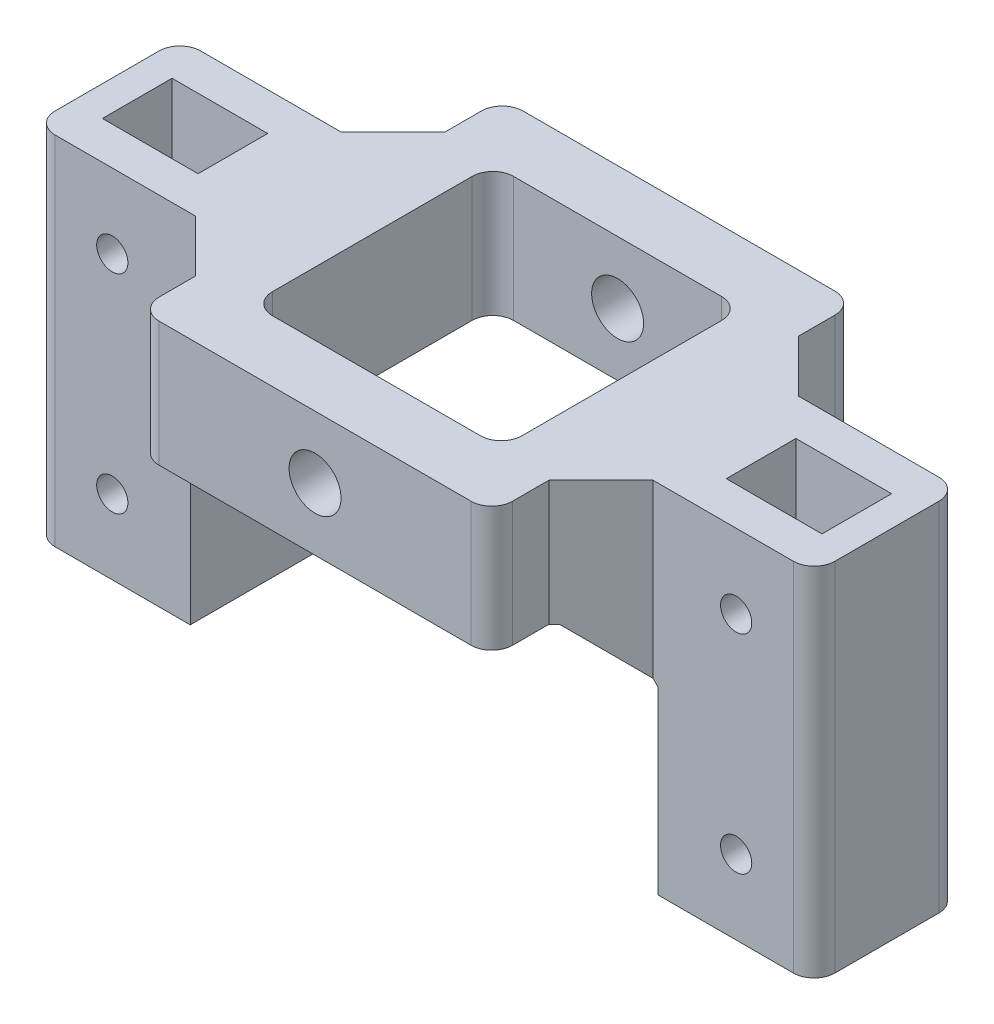
SolidWorks part; units mm, degrees
material "聚脂树脂"
ref_plane "前视基准面" through (0, 0, 0) normal (0, 0, 1) x (1, 0, 0)
ref_plane "上视基准面" through (0, 0, 0) normal (0, 1, 0) x (1, 0, 0)
ref_plane "右视基准面" through (0, 0, 0) normal (1, 0, 0) x (0, 0, -1)
other "Configuration Table"
sketch "草图1" plane through (0, 0, 0) normal (0, 0, 1) x (1, 0, 0)
  line L0 (0, 0) -> (63.4535, 0) construction
  line L5 (-22.5, 17.15) -> (-37.5, -17.15) construction
  line L6 (22.5, -17.15) -> (37.5, -17.15)
  line L7 (0, 0) -> (0, 35.1803) construction
  line L8 (22.5, -17.15) -> (22.5, 17.15)
  line L9 (22.5, 17.15) -> (37.5, 17.15)
  line L10 (37.5, -17.15) -> (37.5, 17.15)
  line L11 (22.5, -17.15) -> (37.5, 17.15) construction
  line L12 (22.5, 17.15) -> (37.5, -17.15) construction
  line L13 (-22.5, -17.15) -> (-37.5, 17.15) construction
  line L14 (-37.5, -17.15) -> (-37.5, 17.15)
  line L15 (-22.5, 17.15) -> (-37.5, 17.15)
  line L16 (-22.5, -17.15) -> (-22.5, 17.15)
  line L17 (-22.5, -17.15) -> (-37.5, -17.15)
  circle A1 centre (30, 10) radius 1.5
  circle A2 centre (30, -10) radius 1.5
  circle A3 centre (-30, -10) radius 1.5
  circle A4 centre (-30, 10) radius 1.5
  point P0 (30, 0)
  point P21 (-30, 0)
  dimension "D3" = 30
  dimension "D4" = 3
  dimension "D1" = 15
  dimension "D2" = 34.3
  dimension "D5" = 30
  dimension "D6" = 10
extrude "凸台-拉伸1" add sketch "草图1" along normal blind 7 and the other way blind 7
sketch "草图2" plane through (0, 17.15, 0) normal (0, 1, 0) x (1, 0, 0)
  line L0 (0, 0) -> (0, 28.9204) construction
  line L1 (0, 0) -> (49.6088, 0) construction
  line L2 (-25.4, 3.35) -> (-34.6, -3.35) construction
  line L3 (25.4, -3.35) -> (34.6, -3.35)
  line L4 (25.4, -3.35) -> (25.4, 3.35)
  line L5 (25.4, 3.35) -> (34.6, 3.35)
  line L6 (34.6, -3.35) -> (34.6, 3.35)
  line L7 (25.4, -3.35) -> (34.6, 3.35) construction
  line L8 (25.4, 3.35) -> (34.6, -3.35) construction
  line L9 (-25.4, -3.35) -> (-34.6, 3.35) construction
  line L10 (-34.6, -3.35) -> (-34.6, 3.35)
  line L11 (-25.4, 3.35) -> (-34.6, 3.35)
  line L12 (-25.4, -3.35) -> (-25.4, 3.35)
  line L13 (-25.4, -3.35) -> (-34.6, -3.35)
  point P3 (30, 0)
  point P13 (-30, 0)
  dimension "D1" = 9.2
  dimension "D2" = 6.7
  dimension "D3" = 30
extrude "切除-拉伸1" cut sketch "草图2" against normal blind 62
sketch "草图3" plane through (0, 17.15, 0) normal (0, 1, 0) x (1, 0, 0)
  line L0 (0, 0) -> (46.7542, 0) construction
  line L1 (0, 0) -> (0, 26.73) construction
  line L2 (22.5, 7) -> (17, 7)
  line L3 (17, 7) -> (17, 17.5)
  line L4 (17, 17.5) -> (-17, 17.5)
  line L6 (-12, 11.6) -> (12, 11.6)
  line L7 (12, 11.6) -> (12, -11.6)
  line L8 (22.5, 7) -> (22.5, -7)
  line L9 (22.5, 7) -> (22.5, -7) construction
  line L10 (-12, -11.6) -> (12, -11.6)
  line L12 (17, -17.5) -> (-17, -17.5)
  line L13 (17, -7) -> (17, -17.5)
  line L14 (22.5, -7) -> (17, -7)
  line L15 (-22.5, -7) -> (-17, -7)
  line L16 (-17, -7) -> (-17, -17.5)
  line L17 (-22.5, 7) -> (-22.5, -7)
  line L18 (-12, 11.6) -> (-12, -11.6)
  line L19 (-17, 7) -> (-17, 17.5)
  line L20 (-22.5, 7) -> (-17, 7)
  point P16 (22.5, 0)
  point P17 (12, 0)
  point P24 (0, -17.5)
  point P25 (0, -11.6)
  point P27 (0, 11.6)
  point P28 (0, 17.5)
  point P29 (-12, 0)
  point P30 (-22.5, 0)
  dimension "D1" = 23.2
  dimension "D2" = 24
  dimension "D3" = 34
  dimension "D4" = 35
extrude "凸台-拉伸2" add sketch "草图3" against normal blind 12
sketch "草图4" plane through (0, 0, 17.5) normal (0, 0, 1) x (1, 0, 0)
  line L0 (0, 0) -> (0, 29.922) construction
  line L1 (-17, 5.15) -> (17, 5.15) construction
  circle A0 centre (0, 11.15) radius 2.5
  dimension "D1" = 5
  dimension "D2" = 6
extrude "切除-拉伸2" cut sketch "草图4" against normal blind 90
sketch "草图6" plane through (0, 0, 7) normal (0, 0, 1) x (1, 0, 0)
  line L0 (0, 0) -> (0, 28.8184) construction
  line L1 (0, 0) -> (51.072, 0) construction
  line L2 (-37.5, 17.15) -> (-37.5, 29.15)
  line L3 (-37.5, 29.15) -> (-22.5, 29.15)
  line L4 (-22.5, 29.15) -> (-22.5, 17.15)
  line L5 (-37.5, 17.15) -> (-17, 17.15) construction
  line L7 (-35, 17.15) -> (-35, 26.65)
  line L8 (-35, 26.65) -> (-25, 26.65)
  line L9 (-25, 26.65) -> (-25, 17.15)
  line L10 (-37.5, 17.15) -> (-35, 17.15)
  line L11 (-25, 17.15) -> (-22.5, 17.15)
  line L12 (25, 26.65) -> (25, 17.15)
  line L13 (35, 26.65) -> (25, 26.65)
  line L14 (35, 17.15) -> (35, 26.65)
  line L15 (37.5, 17.15) -> (35, 17.15)
  line L16 (37.5, 17.15) -> (37.5, 29.15)
  line L17 (37.5, 29.15) -> (22.5, 29.15)
  line L18 (22.5, 29.15) -> (22.5, 17.15)
  line L19 (25, 17.15) -> (22.5, 17.15)
  dimension "D1" = 12
  dimension "D2" = 2.5
fillet "圆角1" radius 2 4 edges at (37.5, 0, -7) (37.5, 0, 7) (-37.5, 0, -7) (-37.5, 0, 7)
chamfer "倒角1" distance 5 angle 45 2 edges at (22.5, 5.15, 0) (-22.5, 5.15, 0)
chamfer "倒角2" distance 5 angle 45 4 edges at (17, 11.15, -7) (-17, 11.15, -7) (17, 11.15, 7) (-17, 11.15, 7)
fillet "圆角2" radius 2 8 edges at (17, 11.15, 17.5) (-17, 11.15, 17.5) (-17, 11.15, -17.5) (17, 11.15, -17.5) (-12, 11.15, 11.6) (12, 11.15, 11.6) (12, 11.15, -11.6) (-12, 11.15, -11.6)
equation "\"5】\"=10"
